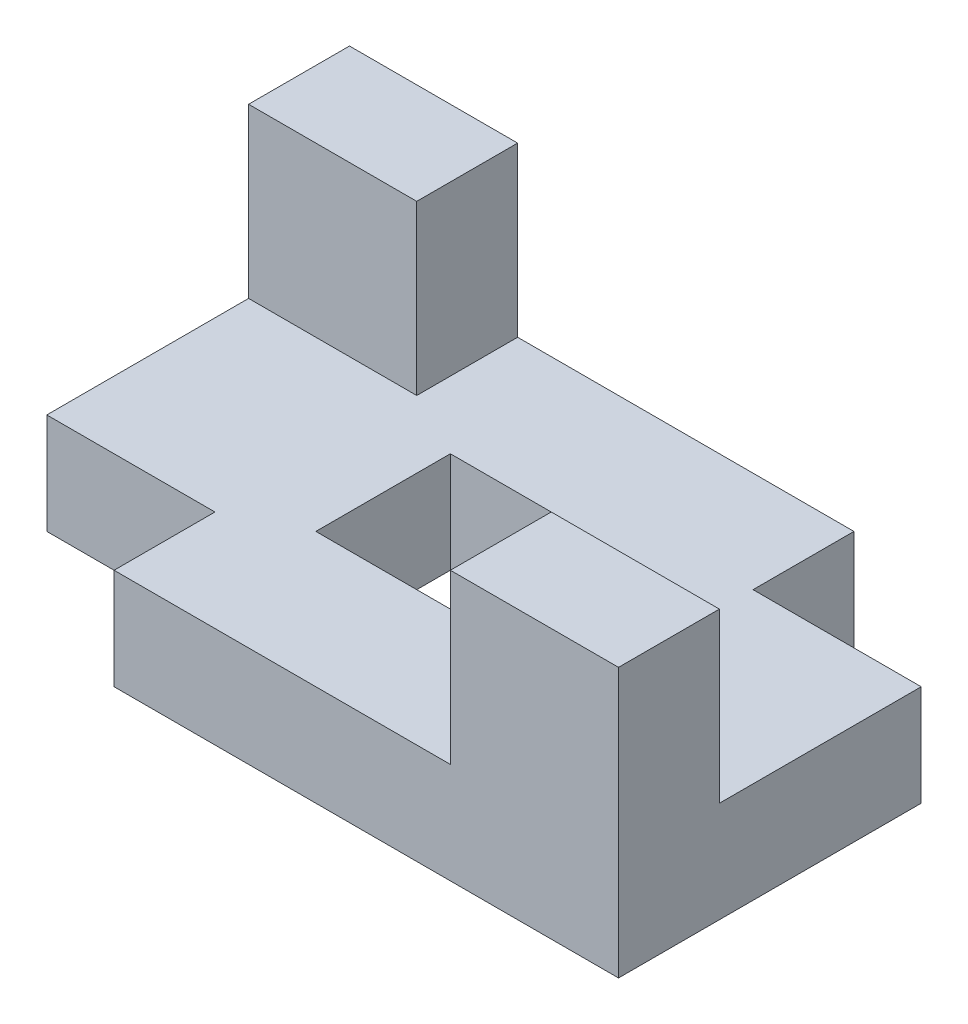
SolidWorks part; units mm, degrees
ref_plane "Front Plane" through (0, 0, 0) normal (0, 0, 1) x (1, 0, 0)
ref_plane "Top Plane" through (0, 0, 0) normal (0, 1, 0) x (1, 0, 0)
ref_plane "Right Plane" through (0, 0, 0) normal (1, 0, 0) x (0, 0, -1)
sketch "Sketch1" plane through (0, 0, 0) normal (0, 1, 0) x (1, 0, 0)
  line L1 (-50, 30) -> (50, 30)
  line L2 (-50, 30) -> (-50, -30)
  line L3 (-50, -30) -> (50, -30)
  line L4 (50, 30) -> (50, -30)
  dimension "D1" = 100
  dimension "D2" = 60
  dimension "D3" = 50
  dimension "D4" = 30
extrude "Boss-Extrude1" add sketch "Sketch1" along normal blind 15
sketch "Sketch2" plane through (0, 15, 0) normal (0, 1, 0) x (1, 0, 0)
  line L1 (-50, 30) -> (-25, 30)
  line L2 (-50, 30) -> (-50, 15)
  line L3 (-50, 15) -> (-25, 15)
  line L4 (-25, 30) -> (-25, 15)
  line L5 (50, -30) -> (25, -30)
  line L6 (50, -30) -> (50, -15)
  line L7 (50, -15) -> (25, -15)
  line L8 (25, -30) -> (25, -15)
  line L9 (-50, -30) -> (-25, -30)
  line L10 (-50, -30) -> (-50, -15)
  line L11 (-50, -15) -> (-25, -15)
  line L12 (-25, -30) -> (-25, -15)
  line L13 (50, 30) -> (25, 30)
  line L14 (50, 30) -> (50, 15)
  line L15 (50, 15) -> (25, 15)
  line L16 (25, 30) -> (25, 15)
  dimension "D1" = 25
  dimension "D2" = 15
extrude "Boss-Extrude2" add sketch "Sketch2" along normal blind 25 contours L4 L3 L2 L1
extrude "Boss-Extrude3" add sketch "Sketch2<3>" along normal blind 25 contours L8 L7 L6 L5
sketch "Sketch2<3>" plane through (0, 15, 0) normal (0, 1, 0) x (1, 0, 0) same geometry as "Sketch2"
extrude "Cut-Extrude1" cut sketch "Sketch2<4>" against normal blind 25 contours L12 L11 L10 L9
sketch "Sketch2<4>" plane through (0, 15, 0) normal (0, 1, 0) x (1, 0, 0) same geometry as "Sketch2"
extrude "Cut-Extrude2" cut sketch "Sketch2<5>" against normal blind 25 contours L16 L15 L14 L13
sketch "Sketch2<5>" plane through (0, 15, 0) normal (0, 1, 0) x (1, 0, 0) same geometry as "Sketch2"
sketch "Sketch4" plane through (0, 15, 0) normal (0, 1, 0) x (1, 0, 0)
  line L0 (-25, -30) -> (25, -30) construction
  line L1 (-15, 10) -> (15, 10)
  line L2 (-15, 10) -> (-15, -10)
  line L3 (-15, -10) -> (15, -10)
  line L4 (15, 10) -> (15, -10)
  line L5 (-50, 15) -> (-50, -15) construction
  dimension "D1" = 20
  dimension "D2" = 35
  dimension "D3" = 30
  dimension "D4" = 20
extrude "Cut-Extrude3" cut sketch "Sketch4" against normal blind 25
